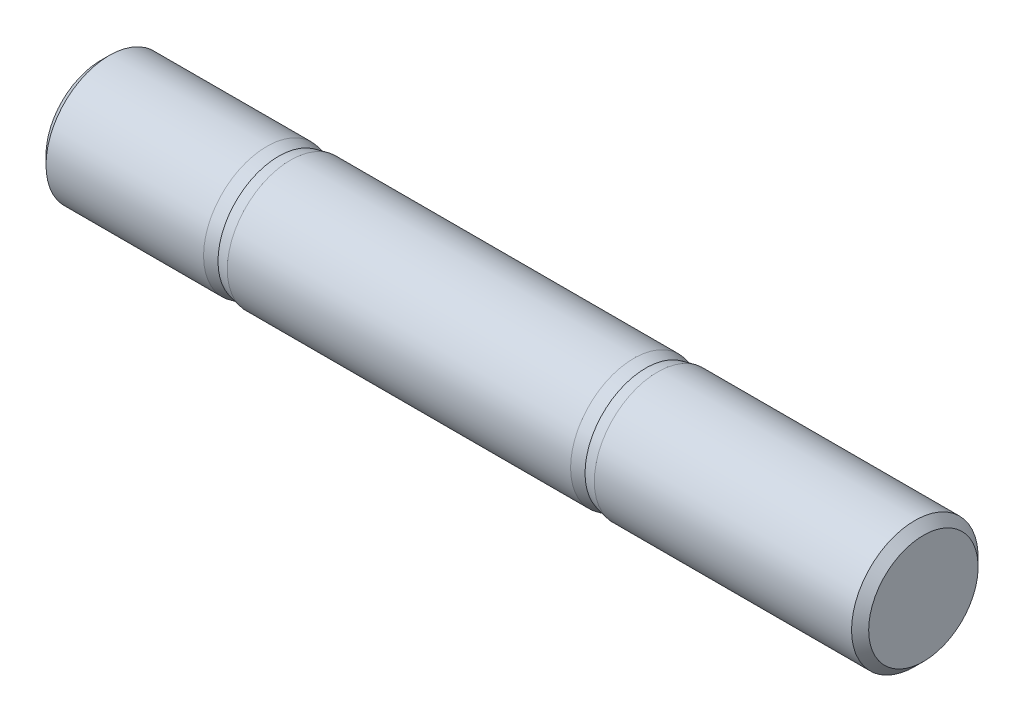
SolidWorks part; units mm, degrees
ref_plane "Front" through (0, 0, 0) normal (0, 0, 1) x (1, 0, 0)
ref_plane "Top" through (0, 0, 0) normal (0, 1, 0) x (1, 0, 0)
ref_plane "Right" through (0, 0, 0) normal (1, 0, 0) x (0, 0, -1)
sketch "Sketch1" plane through (0, 0, 0) normal (0, 0, 1) x (1, 0, 0)
  line L0 (-1.3108, 0) -> (30.3862, 0) construction
  line L1 (0, 0) -> (0, 10)
  line L2 (0, 10) -> (26.25, 10)
  line L3 (26.25, 10) -> (30, 9.188)
  line L4 (30, 9.188) -> (84.25, 9.188)
  line L5 (84.25, 9.188) -> (88, 10)
  line L6 (88, 10) -> (130, 10)
  line L7 (130, 10) -> (130, 0)
  line L8 (130, 0) -> (0, 0)
  dimension "D2" = 3.75
  dimension "l" = 100
  dimension "bm" = 30
  dimension "b" = 42
revolve "BaseHead" add sketch "Sketch1" angle 360 about L0
cosmetic thread "ThreadCosmetic1" [suppressed] parameters "D1"=26.25, "D2"=17.294
cosmetic thread "ThreadCosmetic2" [suppressed] parameters "b"=42, "D2"=17.294
chamfer "HeadChamfer" distance 1.353 angle 45 2 edges at (0, 0, 10) (130, 0, 10)
sketch "Sketch2" plane through (0, 0, 0) normal (0, 0, 1) x (1, 0, 0)
  line L0 (-1.3108, 0) -> (31.2107, 0) construction
  line L2 (26.25, 9.188) -> (30, 10)
  line L3 (30, 10) -> (84.25, 10)
  line L4 (84.25, 10) -> (88, 9.188)
  line L7 (26.25, 10) -> (26.25, -10) construction
  line L9 (26.25, 9.188) -> (88, 9.188)
  line L10 (88, 10) -> (88, -10) construction
  dimension "D2" = 20
  dimension "D1" = 3.75
revolve "BaseBody" add sketch "Sketch2" angle 360 about L0
sketch "Sketch3" plane through (0, 0, 0) normal (0, 0, 1) x (1, 0, 0)
  line L0 (128.647, 8.8283) -> (129.3235, 10)
  line L1 (129.3235, 10) -> (129.3235, 10.5)
  line L2 (129.3235, 10.5) -> (127.9705, 10.5)
  line L3 (127.9705, 10.5) -> (127.9705, 10)
  line L4 (127.9705, 10) -> (128.647, 8.8283)
  line L5 (0, 0) -> (54.5942, 0) construction
  line L6 (128.647, 10) -> (128.647, -10) construction
  dimension "D1" = 60
  dimension "D2" = 60
  dimension "D3" = 0.5
  dimension "D4" = 1.353
  dimension "D5" = 20
revolve "Cut-Revolve10" [suppressed] cut sketch "Sketch3" angle 360 about L5
pattern_linear "LPattern10" [suppressed] count 26 spacing 1.6236 along (-1, 0, 0) of bodies 103
sketch "Sketch4" plane through (0, 0, 0) normal (0, 0, 1) x (1, 0, 0)
  line L0 (1.353, 8.8283) -> (2.0295, 10)
  line L1 (2.0295, 10) -> (2.0295, 10.5)
  line L2 (2.0295, 10.5) -> (0.6765, 10.5)
  line L3 (0.6765, 10.5) -> (0.6765, 10)
  line L4 (0.6765, 10) -> (1.353, 8.8283)
  line L5 (0, 0) -> (16.1581, 0) construction
  line L6 (0, 8.647) -> (0, -8.647) construction
  line L7 (1.353, 10) -> (1.353, -10) construction
  dimension "D1" = 60
  dimension "D2" = 60
  dimension "D3" = 0.5
  dimension "D4" = 1.353
  dimension "D5" = 20
revolve "Cut-Revolve11" [suppressed] cut sketch "Sketch4" angle 360 about L5
pattern_linear "LPattern11" [suppressed] count 16 spacing 1.6236 along (1, 0, 0) of bodies 105
equation "\"D2@Sketch1\" = \"X@Sketch1\""
equation "\"D2@ThreadCosmetic2\" = \"D2@ThreadCosmetic1\""
equation "\"D1@ThreadCosmetic1\" = \"bm@Sketch1\"-\"X@Sketch1\""
equation "\"b@ThreadCosmetic2\" = \"b@Sketch1\""
equation "\"D1@Sketch2\" = \"X@Sketch1\""
equation "\"D2@Sketch2\" = \"d@Sketch1\""
equation "\"D1@HeadChamfer\" =  ( \"d@Sketch1\" - \"D2@ThreadCosmetic1\" )  / 2"
equation "\"D5@Sketch3\" = \"d@Sketch1\""
equation "\"D4@Sketch3\" = (  \"d@Sketch1\" - \"D2@ThreadCosmetic2\" )  / 2"
equation "\"D3@LPattern10\" = \"D4@Sketch3\" * 1.2"
equation "\"D1@LPattern10\" = \"b@ThreadCosmetic2\" / \"D3@LPattern10\""
equation "\"D5@Sketch4\" = \"d@Sketch1\""
equation "\"D4@Sketch4\" = (  \"d@Sketch1\" - \"D2@ThreadCosmetic1\" )  / 2"
equation "\"D3@LPattern11\" = \"D4@Sketch4\" * 1.2"
equation "\"D1@LPattern11\" = \"D1@ThreadCosmetic1\" / \"D3@LPattern11\""
